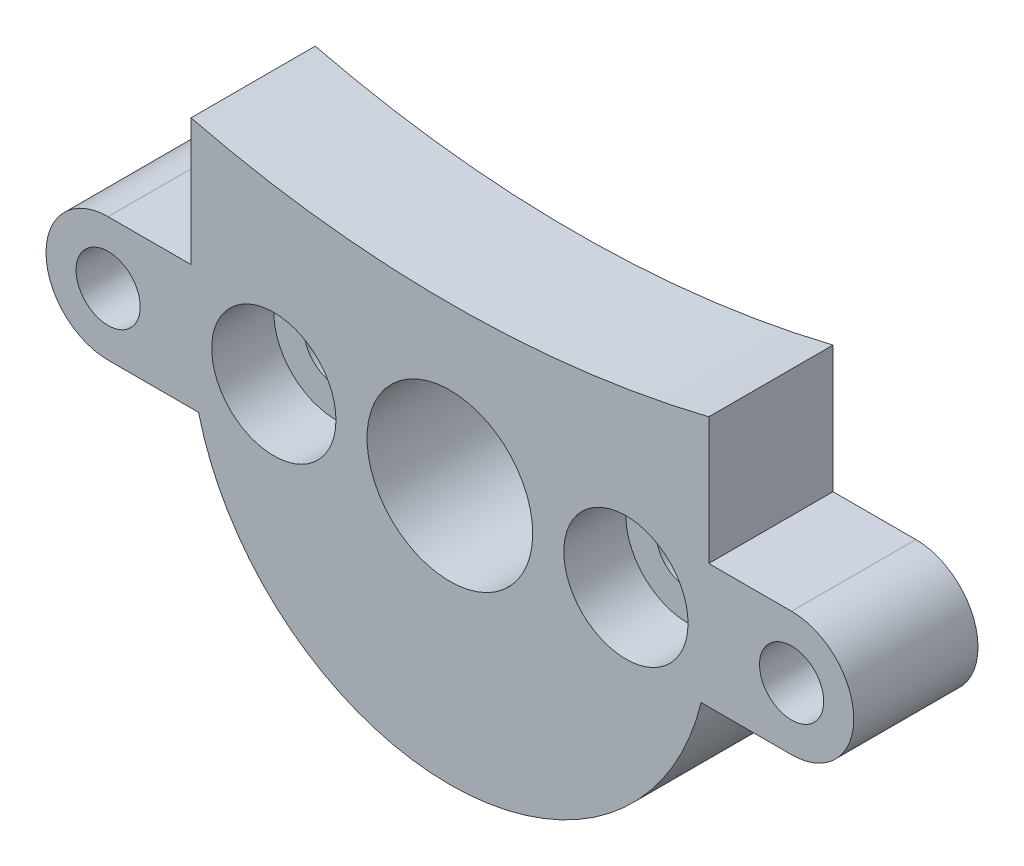
SolidWorks part; units mm, degrees
ref_plane "Front Plane" through (0, 0, 0) normal (0, 0, 1) x (1, 0, 0)
ref_plane "Top Plane" through (0, 0, 0) normal (0, 1, 0) x (1, 0, 0)
ref_plane "Right Plane" through (0, 0, 0) normal (1, 0, 0) x (0, 0, -1)
sketch "Sketch1" plane through (0, 0, 0) normal (0, 0, 1) x (1, 0, 0)
  line L0 (-8.5, 0) -> (8.5, 0) construction
  line L1 (0, 0) -> (0, 60) construction
  line L6 (-8.5, 0) -> (-16.5, 0) construction
  line L7 (8.5, 0) -> (16.5, 0) construction
  line L8 (-16.5, 3) -> (-12.5, 3)
  line L10 (16.5, 3) -> (12.5, 3)
  line L12 (-12.5, 9.1325) -> (-12.5, 3)
  line L13 (12.5, 3) -> (12.5, 9.1325)
  line L14 (16.5, -3) -> (12.1347, -3)
  line L15 (-16.5, -3) -> (-12.1347, -3)
  circle A0 centre (-8.5, 0) radius 1.55
  circle A1 centre (8.5, 0) radius 1.55
  circle A4 centre (0, 60) radius 52.3808 construction
  circle A8 centre (0, 0) radius 4
  arc A16 (-12.5, 0) -> (12.5, 0) centre (0, 0) ccw construction
  arc A17 (-12.5, 9.1325) -> (12.5, 9.1325) centre (0, 60) ccw
  circle A18 centre (-16.5, 0) radius 1.55
  circle A19 centre (16.5, 0) radius 1.55
  arc A21 (-16.5, 3) -> (-16.5, -3) centre (-16.5, 0) ccw
  arc A24 (16.5, 3) -> (16.5, -3) centre (16.5, 0) cw
  arc A25 (-12.1347, -3) -> (12.1347, -3) centre (0, 0) ccw
  point P4 (0, 0)
  point P13 (0, 7.6192)
  point P28 (0, 0)
  point P30 (0, 0)
extrude "Boss-Extrude1" add sketch "Sketch1" along normal blind 6
sketch "Sketch2" plane through (0, 0, 6) normal (0, 0, 1) x (1, 0, 0)
  circle A0 centre (-8.5, 0) radius 3
  circle A1 centre (8.5, 0) radius 3
extrude "Cut-Extrude1" cut sketch "Sketch2" against normal blind 3
